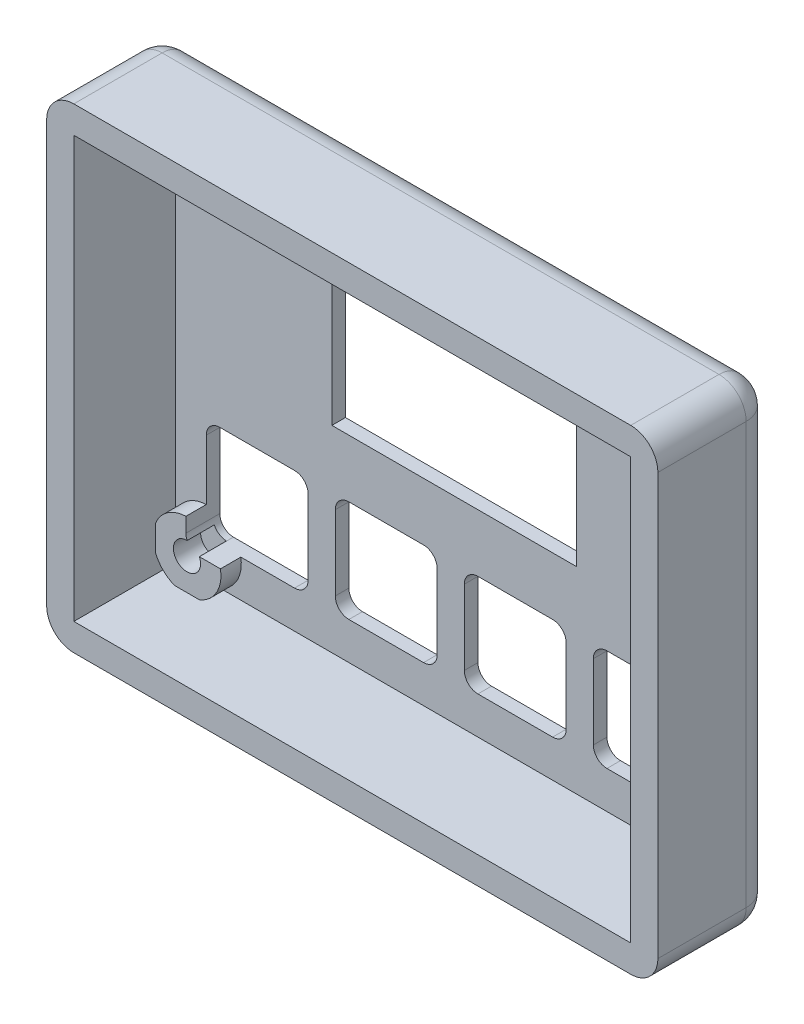
SolidWorks part; units mm, degrees
ref_plane "Front Plane" through (0, 0, 0) normal (0, 0, 1) x (1, 0, 0)
ref_plane "Top Plane" through (0, 0, 0) normal (0, 1, 0) x (1, 0, 0)
ref_plane "Right Plane" through (0, 0, 0) normal (1, 0, 0) x (0, 0, -1)
sketch "Sketch1" plane through (0, 0, 0) normal (0, 0, 1) x (1, 0, 0)
  line L1 (-45, -35) -> (45, -35)
  line L2 (-45, -35) -> (-45, 35)
  line L3 (-45, 35) -> (45, 35)
  line L4 (45, -35) -> (45, 35)
  line L5 (-45, -35) -> (45, 35) construction
  line L6 (-45, 35) -> (45, -35) construction
  point P0 (0, 0)
  dimension "D1" = 90
  dimension "D2" = 70
extrude "Boss-Extrude1" add sketch "Sketch1" along normal blind 2
sketch "Sketch3" plane through (0, 0, 2) normal (0, 0, 1) x (1, 0, 0)
  line L0 (41, -31) -> (41, 31)
  line L1 (41, 31) -> (-41, 31)
  line L2 (-41, 31) -> (-41, -31)
  line L3 (-41, -31) -> (41, -31)
  line L4 (45, -35) -> (45, 35)
  line L5 (45, 35) -> (-45, 35)
  line L6 (-45, 35) -> (-45, -35)
  line L7 (-45, -35) -> (45, -35)
  line L8 (45, -35) -> (45, 35)
  line L9 (45, 35) -> (-45, 35)
  line L10 (-45, 35) -> (-45, -35)
  line L11 (-45, -35) -> (45, -35)
  dimension "D1" = 0
  dimension "D2" = 4
extrude "Boss-Extrude2" add sketch "Sketch3" along normal blind 15
fillet "Fillet1" radius 4 8 edges at (45, -35, 8.5) (-45, 35, 8.5) (45, 35, 8.5) (-45, -35, 8.5) (0, 35, 0) (-45, 0, 0) (0, -35, 0) (45, 0, 0)
sketch "Sketch4" plane through (0, 0, 0) normal (0, 0, -1) x (-1, 0, 0)
  line L0 (0, 10) -> (0, 0) construction
  line L1 (-18, 22) -> (18, 22)
  line L2 (-18, 22) -> (-18, -2)
  line L3 (-18, -2) -> (18, -2)
  line L4 (18, 22) -> (18, -2)
  line L5 (-18, 22) -> (18, -2) construction
  line L6 (-18, -2) -> (18, 22) construction
  point P0 (0, 10)
  dimension "D1" = 24
  dimension "D2" = 36
  dimension "D3" = 10
extrude "Cut-Extrude1" cut sketch "Sketch4" against normal through all
sketch "Sketch2" plane through (0, 0, 2) normal (0, 0, 1) x (1, 0, 0)
  line L1 (-36.34, -26.34) -> (36.34, -26.34) construction
  line L2 (-36.34, -26.34) -> (-36.34, 26.34) construction
  line L3 (-36.34, 26.34) -> (36.34, 26.34) construction
  line L4 (36.34, -26.34) -> (36.34, 26.34) construction
  line L5 (-36.34, -26.34) -> (36.34, 26.34) construction
  line L6 (-36.34, 26.34) -> (36.34, -26.34) construction
  circle A0 centre (-36.34, 26.34) radius 5
  circle A1 centre (36.34, 26.34) radius 5
  circle A2 centre (-36.34, -26.34) radius 5
  circle A3 centre (36.34, -26.34) radius 5
  point P1 (0, 0)
  dimension "D3" = 10
  dimension "D1" = 72.68
  dimension "D2" = 52.68
extrude "Boss-Extrude3" add sketch "Sketch2" along normal blind 3
sketch "Sketch6" plane through (0, 0, 0) normal (0, 0, -1) x (-1, 0, 0)
  line L0 (-41, -31) -> (41, -31) construction
  line L1 (-33.5, -10.5) -> (-22.5, -10.5)
  line L2 (-35.5, -12.5) -> (-35.5, -23.5)
  line L3 (-33.5, -25.5) -> (-22.5, -25.5)
  line L4 (-20.5, -12.5) -> (-20.5, -23.5)
  line L5 (-35.5, -10.5) -> (-20.5, -25.5) construction
  line L6 (-35.5, -25.5) -> (-20.5, -10.5) construction
  line L7 (-41, 31) -> (-41, -31) construction
  line L8 (-14.5, -10.5) -> (-3.5, -10.5)
  line L9 (-16.5, -12.5) -> (-16.5, -23.5)
  line L10 (-14.5, -25.5) -> (-3.5, -25.5)
  line L11 (-1.5, -12.5) -> (-1.5, -23.5)
  line L12 (-16.5, -10.5) -> (-1.5, -25.5) construction
  line L13 (-16.5, -25.5) -> (-1.5, -10.5) construction
  line L14 (4.5, -10.5) -> (15.5, -10.5)
  line L15 (2.5, -12.5) -> (2.5, -23.5)
  line L16 (4.5, -25.5) -> (15.5, -25.5)
  line L17 (17.5, -12.5) -> (17.5, -23.5)
  line L18 (2.5, -10.5) -> (17.5, -25.5) construction
  line L19 (2.5, -25.5) -> (17.5, -10.5) construction
  line L20 (23.5, -10.5) -> (34.5, -10.5)
  line L21 (21.5, -12.5) -> (21.5, -23.5)
  line L22 (23.5, -25.5) -> (34.5, -25.5)
  line L23 (36.5, -12.5) -> (36.5, -23.5)
  line L24 (21.5, -10.5) -> (36.5, -25.5) construction
  line L25 (21.5, -25.5) -> (36.5, -10.5) construction
  arc A0 (-35.5, -23.5) -> (-33.5, -25.5) centre (-33.5, -23.5) ccw
  arc A1 (-22.5, -25.5) -> (-20.5, -23.5) centre (-22.5, -23.5) ccw
  arc A2 (-22.5, -10.5) -> (-20.5, -12.5) centre (-22.5, -12.5) cw
  arc A3 (-33.5, -10.5) -> (-35.5, -12.5) centre (-33.5, -12.5) ccw
  arc A4 (-16.5, -23.5) -> (-14.5, -25.5) centre (-14.5, -23.5) ccw
  arc A5 (-3.5, -25.5) -> (-1.5, -23.5) centre (-3.5, -23.5) ccw
  arc A6 (-3.5, -10.5) -> (-1.5, -12.5) centre (-3.5, -12.5) cw
  arc A7 (-14.5, -10.5) -> (-16.5, -12.5) centre (-14.5, -12.5) ccw
  arc A8 (2.5, -23.5) -> (4.5, -25.5) centre (4.5, -23.5) ccw
  arc A9 (15.5, -25.5) -> (17.5, -23.5) centre (15.5, -23.5) ccw
  arc A10 (15.5, -10.5) -> (17.5, -12.5) centre (15.5, -12.5) cw
  arc A11 (4.5, -10.5) -> (2.5, -12.5) centre (4.5, -12.5) ccw
  arc A12 (21.5, -23.5) -> (23.5, -25.5) centre (23.5, -23.5) ccw
  arc A13 (34.5, -25.5) -> (36.5, -23.5) centre (34.5, -23.5) ccw
  arc A14 (34.5, -10.5) -> (36.5, -12.5) centre (34.5, -12.5) cw
  arc A15 (23.5, -10.5) -> (21.5, -12.5) centre (23.5, -12.5) ccw
  point P0 (-28, -18)
  point P17 (-9, -18)
  point P39 (10, -18)
  point P56 (29, -18)
  dimension "D2" = 2
  dimension "D1" = 15
  dimension "D3" = 13
  dimension "D4" = 13
  dimension "D5" = 4
extrude "Cut-Extrude2" cut sketch "Sketch6" against normal blind 18
sketch "Sketch7" plane through (0, 0, 5) normal (0, 0, 1) x (1, 0, 0)
  circle A0 centre (-36.34, 26.34) radius 2
  circle A1 centre (36.34, 26.34) radius 2
  circle A2 centre (36.34, -26.34) radius 2
  circle A3 centre (-36.34, -26.34) radius 2
  dimension "D1" = 4
extrude "Cut-Extrude3" cut sketch "Sketch7" against normal blind 4
